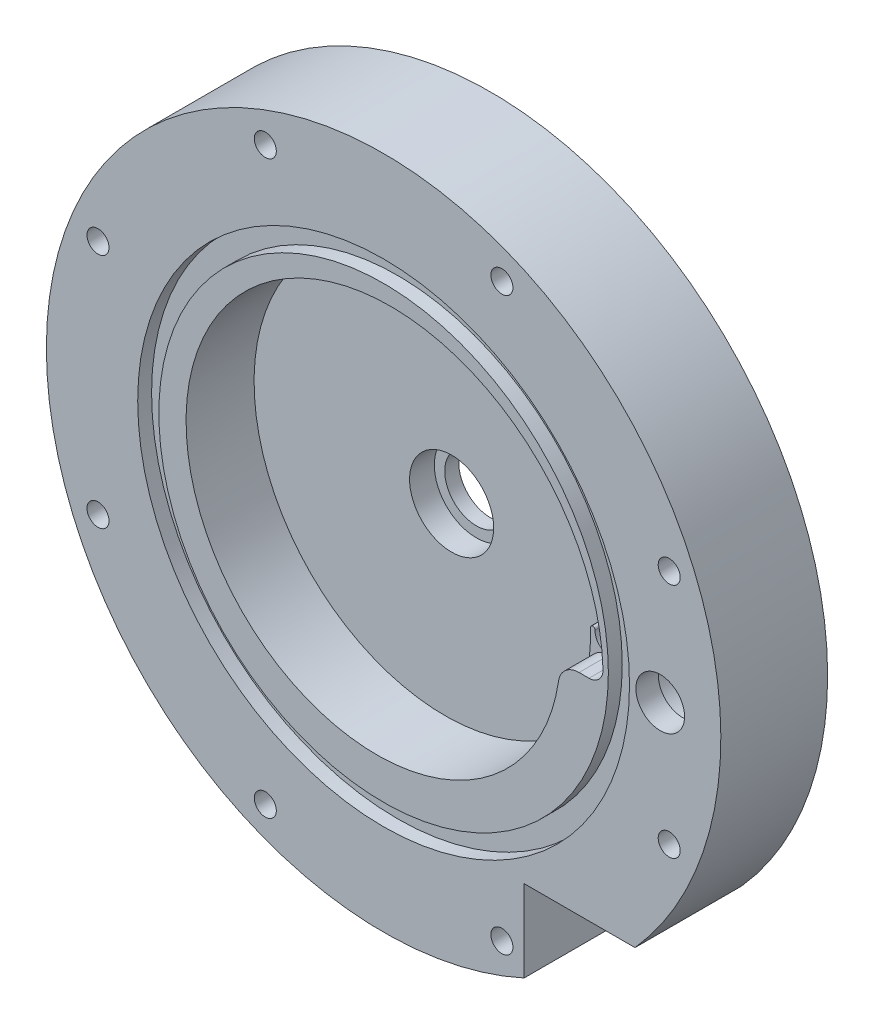
SolidWorks part; units mm, degrees
material "6061-T6 (SS)"
ref_plane "Front Plane" through (0, 0, 0) normal (0, 0, 1) x (1, 0, 0)
ref_plane "Top Plane" through (0, 0, 0) normal (0, 1, 0) x (1, 0, 0)
ref_plane "Right Plane" through (0, 0, 0) normal (1, 0, 0) x (0, 0, -1)
sketch "Sketch22" plane through (0, 0, 0) normal (0, 1, 0) x (1, 0, 0)
  line L0 (-25.4, 0) -> (-9.5, 0)
  line L1 (-25.4, 0) -> (-25.4, -15.367)
  line L3 (-25.4, -15.367) -> (-76.2, -15.367)
  line L4 (-76.2, -15.367) -> (-76.2, 8.763)
  line L5 (-9.5, 0) -> (-9.5, 5.588)
  line L7 (-9.5, 5.588) -> (-7.1437, 5.588)
  line L8 (-7.1437, 5.588) -> (-7.1437, 8.763)
  line L9 (-7.1437, 8.763) -> (-76.2, 8.763)
  line L10 (0, 0) -> (0, 9.525) construction
  dimension "D1" = 14.2875
  dimension "D2" = 19
  dimension "D4" = 3.175
  dimension "D5" = 50.8
  dimension "D6" = 152.4
  dimension "D7" = 24.13
  dimension ".27" = 5.588
revolve "Main Body" add sketch "Sketch22" angle 360 about L10
curve "Volute Spiral"
sketch "Sketch23" plane through (0, 0, 0) normal (0, 0, 1) x (1, 0, 0)
  line L0 (44.1669, -3.2789) -> (46.41, -3.2789)
  arc A1 (40.9936, 0) -> (44.1669, -3.2789) centre (44.1669, -0.1039) ccw
  arc A2 (39.9395, 0) -> (40.9936, 0) centre (40.4666, 0.0173) cw
  arc A4 (46.41, -3.2789) -> (49.578, 0) centre (46.41, -0.1091) ccw
  spline S0 degree 3 poles (2036.7889, 105.1389) (27.9917, 30.1612) (39.5671, 15.0372) (39.954, -0.5026) (39.9588, -0.7541) (39.9652, -1.2573) (39.9616, -2.517) (39.8751, -4.3652) (39.6495, -6.5428) (39.3399, -8.5438) (38.9295, -10.5302) (38.4188, -12.497) (37.8089, -14.4391) (37.1009, -16.3516) (36.2962, -18.2293) (35.3965, -20.0675) (34.4038, -21.8614) (33.3202, -23.6061) (32.1481, -25.2972) (30.8902, -26.9301) (29.5494, -28.5005) (28.1288, -30.0042) (26.6317, -31.4371) (25.0616, -32.7952) (23.4223, -34.075) (21.7176, -35.2728) (19.9517, -36.3854) (18.1288, -37.4095) (16.2533, -38.3423) (14.3299, -39.1811) (12.3632, -39.9234) (10.3581, -40.5669) (8.3195, -41.1098) (6.2525, -41.5501) (4.1622, -41.8865) (2.054, -42.1178) (-0.0671, -42.2429) (-2.1955, -42.2611) (-4.3259, -42.1721) (-6.4529, -41.9757) (-8.5711, -41.6719) (-10.675, -41.2613) (-12.7593, -40.7443) (-14.8186, -40.1221) (-16.8476, -39.3958) (-18.841, -38.5668) (-20.7936, -37.6369) (-22.7003, -36.6081) (-24.5561, -35.4827) (-26.3561, -34.2632) (-28.0956, -32.9524) (-29.7698, -31.5532) (-31.3743, -30.0689) (-32.9048, -28.503) (-34.357, -26.8593) (-35.7272, -25.1415) (-37.0114, -23.3537) (-38.2061, -21.5004) (-39.308, -19.586) (-40.314, -17.615) (-41.221, -15.5925) (-42.0265, -13.5232) (-42.7281, -11.4123) (-43.3237, -9.265) (-43.8112, -7.0867) (-44.1892, -4.8828) (-44.4563, -2.6588) (-44.6113, -0.4202) (-44.6537, 1.8272) (-44.5827, 4.0778) (-44.3982, 6.3259) (-44.1003, 8.5657) (-43.6894, 10.7916) (-43.1661, 12.9978) (-42.5313, 15.1786) (-41.7863, 17.3284) (-40.9326, 19.4417) (-39.9719, 21.5129) (-38.9064, 23.5366) (-37.7384, 25.5075) (-36.4705, 27.4204) (-35.1055, 29.2703) (-33.6468, 31.0522) (-32.0975, 32.7613) (-30.4614, 34.3932) (-28.7423, 35.9432) (-26.9442, 37.4073) (-25.0716, 38.7814) (-23.1289, 40.0617) (-21.1208, 41.2447) (-19.0521, 42.3269) (-16.928, 43.3053) (-14.7537, 44.177) (-12.5345, 44.9396) (-10.2758, 45.5905) (-7.9834, 46.1279) (-5.6629, 46.55) (-3.3202, 46.8552) (-0.9611, 47.0425) (1.4085, 47.1109) (3.7826, 47.06) (6.155, 46.8893) (8.5199, 46.5989) (10.8711, 46.1892) (13.2026, 45.6608) (15.5084, 45.0146) (17.7826, 44.252) (20.0193, 43.3744) (22.2127, 42.3836) (24.357, 41.2819) (26.4467, 40.0717) (28.4762, 38.7556) (30.4402, 37.3367) (32.3334, 35.8182) (34.1508, 34.2036) (35.8876, 32.4968) (37.539, 30.7018) (39.1006, 28.8228) (40.568, 26.8643) (41.9373, 24.8311) (43.2047, 22.7281) (44.3665, 20.5604) (45.4195, 18.3333) (46.3606, 16.0523) (47.1871, 13.7229) (47.8965, 11.351) (48.4866, 8.9424) (48.9555, 6.5032) (49.2727, 4.2452) (49.431, 2.5929) (49.4967, 1.6609) (49.522, 1.2461) (49.539, 0.9348) (49.554, 0.6234) (50.3116, -17.2348) (38.9556, -35.4442) (2048.9371, 22.4075) knots -0.163415 -0.163415 -0.163415 -0.163415 0.000895 0.001791 0.002687 0.003583 0.007168 0.016147 0.023344 0.030554 0.037776 0.045012 0.05226 0.059521 0.066796 0.074083 0.081383 0.088697 0.096023 0.103362 0.110715 0.118081 0.12546 0.132852 0.140257 0.147676 0.155108 0.162553 0.170011 0.177483 0.184968 0.192466 0.199978 0.207503 0.215042 0.222594 0.230159 0.237738 0.245331 0.252937 0.260556 0.268189 0.275836 0.283496 0.291169 0.298857 0.306558 0.314272 0.322 0.329742 0.337497 0.345267 0.353049 0.360846 0.368656 0.37648 0.384318 0.39217 0.400035 0.407914 0.415807 0.423714 0.431634 0.439569 0.447517 0.455479 0.463455 0.471445 0.479449 0.487467 0.495499 0.503544 0.511604 0.519677 0.527765 0.535867 0.543982 0.552112 0.560256 0.568413 0.576585 0.584771 0.592971 0.601185 0.609413 0.617655 0.625911 0.634182 0.642466 0.650765 0.659078 0.667405 0.675747 0.684102 0.692472 0.700856 0.709254 0.717666 0.726093 0.734534 0.742989 0.751459 0.759943 0.768441 0.776953 0.78548 0.794021 0.802577 0.811146 0.819731 0.828329 0.836942 0.845569 0.854211 0.862867 0.871538 0.880223 0.888922 0.897636 0.906365 0.915108 0.923865 0.932637 0.941423 0.950224 0.95904 0.967869 0.976714 0.985573 0.992227 0.994447 0.995557 0.996667 0.997778 0.998889 1.187662 1.187662 1.187662 1.187662 only from (39.9395, 0) to (49.578, 0) construction
  spline S1 degree 3 poles (39.9395, 0) (39.9423, -0.0837) (39.9478, -0.2513) (39.954, -0.5026) (39.9588, -0.7541) (39.9652, -1.2573) (39.9616, -2.517) (39.8751, -4.3652) (39.6495, -6.5428) (39.3399, -8.5438) (38.9295, -10.5302) (38.4188, -12.497) (37.8089, -14.4391) (37.1009, -16.3516) (36.2962, -18.2293) (35.3965, -20.0675) (34.4038, -21.8614) (33.3202, -23.6061) (32.1481, -25.2972) (30.8902, -26.9301) (29.5494, -28.5005) (28.1288, -30.0042) (26.6317, -31.4371) (25.0616, -32.7952) (23.4223, -34.075) (21.7176, -35.2728) (19.9517, -36.3854) (18.1288, -37.4095) (16.2533, -38.3423) (14.3299, -39.1811) (12.3632, -39.9234) (10.3581, -40.5669) (8.3195, -41.1098) (6.2525, -41.5501) (4.1622, -41.8865) (2.054, -42.1178) (-0.0671, -42.2429) (-2.1955, -42.2611) (-4.3259, -42.1721) (-6.4529, -41.9757) (-8.5711, -41.6719) (-10.675, -41.2613) (-12.7593, -40.7443) (-14.8186, -40.1221) (-16.8476, -39.3958) (-18.841, -38.5668) (-20.7936, -37.6369) (-22.7003, -36.6081) (-24.5561, -35.4827) (-26.3561, -34.2632) (-28.0956, -32.9524) (-29.7698, -31.5532) (-31.3743, -30.0689) (-32.9048, -28.503) (-34.357, -26.8593) (-35.7272, -25.1415) (-37.0114, -23.3537) (-38.2061, -21.5004) (-39.308, -19.586) (-40.314, -17.615) (-41.221, -15.5925) (-42.0265, -13.5232) (-42.7281, -11.4123) (-43.3237, -9.265) (-43.8112, -7.0867) (-44.1892, -4.8828) (-44.4563, -2.6588) (-44.6113, -0.4202) (-44.6537, 1.8272) (-44.5827, 4.0778) (-44.3982, 6.3259) (-44.1003, 8.5657) (-43.6894, 10.7916) (-43.1661, 12.9978) (-42.5313, 15.1786) (-41.7863, 17.3284) (-40.9326, 19.4417) (-39.9719, 21.5129) (-38.9064, 23.5366) (-37.7384, 25.5075) (-36.4705, 27.4204) (-35.1055, 29.2703) (-33.6468, 31.0522) (-32.0975, 32.7613) (-30.4614, 34.3932) (-28.7423, 35.9432) (-26.9442, 37.4073) (-25.0716, 38.7814) (-23.1289, 40.0617) (-21.1208, 41.2447) (-19.0521, 42.3269) (-16.928, 43.3053) (-14.7537, 44.177) (-12.5345, 44.9396) (-10.2758, 45.5905) (-7.9834, 46.1279) (-5.6629, 46.55) (-3.3202, 46.8552) (-0.9611, 47.0425) (1.4085, 47.1109) (3.7826, 47.06) (6.155, 46.8893) (8.5199, 46.5989) (10.8711, 46.1892) (13.2026, 45.6608) (15.5084, 45.0146) (17.7826, 44.252) (20.0193, 43.3744) (22.2127, 42.3836) (24.357, 41.2819) (26.4467, 40.0717) (28.4762, 38.7556) (30.4402, 37.3367) (32.3334, 35.8182) (34.1508, 34.2036) (35.8876, 32.4968) (37.539, 30.7018) (39.1006, 28.8228) (40.568, 26.8643) (41.9373, 24.8311) (43.2047, 22.7281) (44.3665, 20.5604) (45.4195, 18.3333) (46.3606, 16.0523) (47.1871, 13.7229) (47.8965, 11.351) (48.4866, 8.9424) (48.9555, 6.5032) (49.2727, 4.2452) (49.431, 2.5929) (49.4967, 1.6609) (49.522, 1.2461) (49.539, 0.9348) (49.554, 0.6234) (49.5673, 0.3117) (49.5744, 0.1039) (49.578, 0) knots 0 0 0 0 0.000895 0.001791 0.002687 0.003583 0.007168 0.016147 0.023344 0.030554 0.037776 0.045012 0.05226 0.059521 0.066796 0.074083 0.081383 0.088697 0.096023 0.103362 0.110715 0.118081 0.12546 0.132852 0.140257 0.147676 0.155108 0.162553 0.170011 0.177483 0.184968 0.192466 0.199978 0.207503 0.215042 0.222594 0.230159 0.237738 0.245331 0.252937 0.260556 0.268189 0.275836 0.283496 0.291169 0.298857 0.306558 0.314272 0.322 0.329742 0.337497 0.345267 0.353049 0.360846 0.368656 0.37648 0.384318 0.39217 0.400035 0.407914 0.415807 0.423714 0.431634 0.439569 0.447517 0.455479 0.463455 0.471445 0.479449 0.487467 0.495499 0.503544 0.511604 0.519677 0.527765 0.535867 0.543982 0.552112 0.560256 0.568413 0.576585 0.584771 0.592971 0.601185 0.609413 0.617655 0.625911 0.634182 0.642466 0.650765 0.659078 0.667405 0.675747 0.684102 0.692472 0.700856 0.709254 0.717666 0.726093 0.734534 0.742989 0.751459 0.759943 0.768441 0.776953 0.78548 0.794021 0.802577 0.811146 0.819731 0.828329 0.836942 0.845569 0.854211 0.862867 0.871538 0.880223 0.888922 0.897636 0.906365 0.915108 0.923865 0.932637 0.941423 0.950224 0.95904 0.967869 0.976714 0.985573 0.992227 0.994447 0.995557 0.996667 0.997778 0.998889 1 1 1 1
  dimension "D1" = 3.175
  dimension "D2" = 1.0541
extrude "Volute Cut" cut sketch "Sketch23" along normal through all
ref_plane "Volute Height Plane" through (0, 0, 8.5827) normal (0, 0, 1) x (1, 0, 0)
sketch "Sketch25" plane through (0, 0, 8.5827) normal (0, 0, 1) x (1, 0, 0)
  arc A0 (44.1669, -3.2789) -> (39.5302, -7.28) centre (44.1669, -7.9661) ccw
  arc A1 (46.41, -3.2789) -> (49.578, 0) centre (46.41, -0.1091) ccw construction
  arc A2 (46.41, -3.2789) -> (49.578, 0) centre (46.41, -0.1091) ccw
  arc A3 (40.9936, 0) -> (39.9395, 0) centre (40.4666, 0.0173) ccw construction
  arc A4 (40.9936, 0) -> (44.1669, -3.2789) centre (44.1669, -0.1039) ccw construction
  arc A5 (40.9936, 0) -> (39.9395, 0) centre (40.4666, 0.0173) ccw
  arc A6 (40.9936, 0) -> (44.1669, -3.2789) centre (44.1669, -0.1039) ccw
  spline S1 degree 3 poles (2048.8734, 22.4056) (38.9558, -35.4438) (50.3115, -17.2346) (49.554, 0.6234) (49.539, 0.9348) (49.522, 1.2461) (49.4967, 1.6609) (49.431, 2.5929) (49.2727, 4.2452) (48.9555, 6.5032) (48.4866, 8.9424) (47.8965, 11.351) (47.1871, 13.7229) (46.3606, 16.0523) (45.4195, 18.3333) (44.3665, 20.5604) (43.2047, 22.7281) (41.9373, 24.8311) (40.568, 26.8643) (39.1006, 28.8228) (37.539, 30.7018) (35.8876, 32.4968) (34.1508, 34.2036) (32.3334, 35.8182) (30.4402, 37.3367) (28.4762, 38.7556) (26.4467, 40.0717) (24.357, 41.2819) (22.2127, 42.3836) (20.0193, 43.3744) (17.7826, 44.252) (15.5084, 45.0146) (13.2026, 45.6608) (10.8711, 46.1892) (8.5199, 46.5989) (6.155, 46.8893) (3.7826, 47.06) (1.4085, 47.1109) (-0.9611, 47.0425) (-3.3202, 46.8552) (-5.6629, 46.55) (-7.9834, 46.1279) (-10.2758, 45.5905) (-12.5345, 44.9396) (-14.7537, 44.177) (-16.928, 43.3053) (-19.0521, 42.3269) (-21.1208, 41.2447) (-23.1289, 40.0617) (-25.0716, 38.7814) (-26.9442, 37.4073) (-28.7423, 35.9432) (-30.4614, 34.3932) (-32.0975, 32.7613) (-33.6468, 31.0522) (-35.1055, 29.2703) (-36.4705, 27.4204) (-37.7384, 25.5075) (-38.9064, 23.5366) (-39.9719, 21.5129) (-40.9326, 19.4417) (-41.7863, 17.3284) (-42.5313, 15.1786) (-43.1661, 12.9978) (-43.6894, 10.7916) (-44.1003, 8.5657) (-44.3982, 6.3259) (-44.5827, 4.0778) (-44.6537, 1.8272) (-44.6113, -0.4202) (-44.4563, -2.6588) (-44.1892, -4.8828) (-43.8112, -7.0867) (-43.3237, -9.265) (-42.7281, -11.4123) (-42.0265, -13.5232) (-41.221, -15.5925) (-40.314, -17.615) (-39.308, -19.586) (-38.2061, -21.5004) (-37.0114, -23.3537) (-35.7272, -25.1415) (-34.357, -26.8593) (-32.9048, -28.503) (-31.3743, -30.0689) (-29.7698, -31.5532) (-28.0956, -32.9524) (-26.3561, -34.2632) (-24.5561, -35.4827) (-22.7003, -36.6081) (-20.7936, -37.6369) (-18.841, -38.5668) (-16.8476, -39.3958) (-14.8186, -40.1221) (-12.7593, -40.7443) (-10.675, -41.2613) (-8.5711, -41.6719) (-6.4529, -41.9757) (-4.3259, -42.1721) (-2.1955, -42.2611) (-0.0671, -42.2429) (2.054, -42.1178) (4.1622, -41.8865) (6.2525, -41.5501) (8.3195, -41.1098) (10.3581, -40.5669) (12.3632, -39.9234) (14.3299, -39.1811) (16.2533, -38.3423) (18.1288, -37.4095) (19.9517, -36.3854) (21.7176, -35.2728) (23.4223, -34.075) (25.0616, -32.7952) (26.6317, -31.4371) (28.1288, -30.0042) (29.5494, -28.5005) (30.8902, -26.9301) (32.1481, -25.2972) (33.3202, -23.6061) (34.4038, -21.8614) (35.3965, -20.0675) (36.2962, -18.2293) (37.1009, -16.3516) (37.8089, -14.4391) (38.4188, -12.497) (38.9295, -10.5302) (39.3399, -8.5438) (39.6495, -6.5428) (39.8751, -4.3652) (39.9616, -2.517) (39.9652, -1.2573) (39.9588, -0.7541) (39.954, -0.5026) (39.5671, 15.0364) (27.9928, 30.1597) (2036.501, 105.1281) knots -0.18766 -0.18766 -0.18766 -0.18766 0.001111 0.002222 0.003333 0.004443 0.005553 0.007773 0.014427 0.023286 0.032131 0.04096 0.049776 0.058577 0.067363 0.076135 0.084892 0.093635 0.102364 0.111078 0.119777 0.128462 0.137133 0.145789 0.154431 0.163058 0.171671 0.180269 0.188854 0.197423 0.205979 0.21452 0.223047 0.231559 0.240057 0.248541 0.257011 0.265466 0.273907 0.282334 0.290746 0.299144 0.307528 0.315898 0.324253 0.332595 0.340922 0.349235 0.357534 0.365818 0.374089 0.382345 0.390587 0.398815 0.407029 0.415229 0.423415 0.431587 0.439744 0.447888 0.456018 0.464133 0.472235 0.480323 0.488396 0.496456 0.504501 0.512533 0.520551 0.528555 0.536545 0.544521 0.552483 0.560431 0.568366 0.576286 0.584193 0.592086 0.599965 0.60783 0.615682 0.62352 0.631344 0.639154 0.646951 0.654733 0.662503 0.670258 0.678 0.685728 0.693442 0.701143 0.708831 0.716504 0.724164 0.731811 0.739444 0.747063 0.754669 0.762262 0.769841 0.777406 0.784958 0.792497 0.800022 0.807534 0.815032 0.822517 0.829989 0.837447 0.844892 0.852324 0.859743 0.867148 0.87454 0.881919 0.889285 0.896638 0.903977 0.911303 0.918617 0.925917 0.933204 0.940479 0.94774 0.954988 0.962224 0.969446 0.976656 0.983853 0.992832 0.996417 0.997313 0.998209 0.999105 1.163407 1.163407 1.163407 1.163407 only from (49.578, 0) to (39.9395, 0) construction
  spline S2 degree 3 poles (49.578, 0) (49.5744, 0.1039) (49.5673, 0.3117) (49.554, 0.6234) (49.539, 0.9348) (49.522, 1.2461) (49.4967, 1.6609) (49.431, 2.5929) (49.2727, 4.2452) (48.9555, 6.5032) (48.4866, 8.9424) (47.8965, 11.351) (47.1871, 13.7229) (46.3606, 16.0523) (45.4195, 18.3333) (44.3665, 20.5604) (43.2047, 22.7281) (41.9373, 24.8311) (40.568, 26.8643) (39.1006, 28.8228) (37.539, 30.7018) (35.8876, 32.4968) (34.1508, 34.2036) (32.3334, 35.8182) (30.4402, 37.3367) (28.4762, 38.7556) (26.4467, 40.0717) (24.357, 41.2819) (22.2127, 42.3836) (20.0193, 43.3744) (17.7826, 44.252) (15.5084, 45.0146) (13.2026, 45.6608) (10.8711, 46.1892) (8.5199, 46.5989) (6.155, 46.8893) (3.7826, 47.06) (1.4085, 47.1109) (-0.9611, 47.0425) (-3.3202, 46.8552) (-5.6629, 46.55) (-7.9834, 46.1279) (-10.2758, 45.5905) (-12.5345, 44.9396) (-14.7537, 44.177) (-16.928, 43.3053) (-19.0521, 42.3269) (-21.1208, 41.2447) (-23.1289, 40.0617) (-25.0716, 38.7814) (-26.9442, 37.4073) (-28.7423, 35.9432) (-30.4614, 34.3932) (-32.0975, 32.7613) (-33.6468, 31.0522) (-35.1055, 29.2703) (-36.4705, 27.4204) (-37.7384, 25.5075) (-38.9064, 23.5366) (-39.9719, 21.5129) (-40.9326, 19.4417) (-41.7863, 17.3284) (-42.5313, 15.1786) (-43.1661, 12.9978) (-43.6894, 10.7916) (-44.1003, 8.5657) (-44.3982, 6.3259) (-44.5827, 4.0778) (-44.6537, 1.8272) (-44.6113, -0.4202) (-44.4563, -2.6588) (-44.1892, -4.8828) (-43.8112, -7.0867) (-43.3237, -9.265) (-42.7281, -11.4123) (-42.0265, -13.5232) (-41.221, -15.5925) (-40.314, -17.615) (-39.308, -19.586) (-38.2061, -21.5004) (-37.0114, -23.3537) (-35.7272, -25.1415) (-34.357, -26.8593) (-32.9048, -28.503) (-31.3743, -30.0689) (-29.7698, -31.5532) (-28.0956, -32.9524) (-26.3561, -34.2632) (-24.5561, -35.4827) (-22.7003, -36.6081) (-20.7936, -37.6369) (-18.841, -38.5668) (-16.8476, -39.3958) (-14.8186, -40.1221) (-12.7593, -40.7443) (-10.675, -41.2613) (-8.5711, -41.6719) (-6.4529, -41.9757) (-4.3259, -42.1721) (-2.1955, -42.2611) (-0.0671, -42.2429) (2.054, -42.1178) (4.1622, -41.8865) (6.2525, -41.5501) (8.3195, -41.1098) (10.3581, -40.5669) (12.3632, -39.9234) (14.3299, -39.1811) (16.2533, -38.3423) (18.1288, -37.4095) (19.9517, -36.3854) (21.7176, -35.2728) (23.4223, -34.075) (25.0616, -32.7952) (26.6317, -31.4371) (28.1288, -30.0042) (29.5494, -28.5005) (30.8902, -26.9301) (32.1481, -25.2972) (33.3202, -23.6061) (34.4038, -21.8614) (35.3965, -20.0675) (36.2962, -18.2293) (37.1009, -16.3516) (37.8089, -14.4391) (38.4188, -12.497) (38.9295, -10.5302) (39.3399, -8.5438) (39.6495, -6.5428) (39.8751, -4.3652) (39.9616, -2.517) (39.9652, -1.2573) (39.9588, -0.7541) (39.954, -0.5026) (39.9478, -0.2513) (39.9423, -0.0837) (39.9395, 0) knots 0 0 0 0 0.001111 0.002222 0.003333 0.004443 0.005553 0.007773 0.014427 0.023286 0.032131 0.04096 0.049776 0.058577 0.067363 0.076135 0.084892 0.093635 0.102364 0.111078 0.119777 0.128462 0.137133 0.145789 0.154431 0.163058 0.171671 0.180269 0.188854 0.197423 0.205979 0.21452 0.223047 0.231559 0.240057 0.248541 0.257011 0.265466 0.273907 0.282334 0.290746 0.299144 0.307528 0.315898 0.324253 0.332595 0.340922 0.349235 0.357534 0.365818 0.374089 0.382345 0.390587 0.398815 0.407029 0.415229 0.423415 0.431587 0.439744 0.447888 0.456018 0.464133 0.472235 0.480323 0.488396 0.496456 0.504501 0.512533 0.520551 0.528555 0.536545 0.544521 0.552483 0.560431 0.568366 0.576286 0.584193 0.592086 0.599965 0.60783 0.615682 0.62352 0.631344 0.639154 0.646951 0.654733 0.662503 0.670258 0.678 0.685728 0.693442 0.701143 0.708831 0.716504 0.724164 0.731811 0.739444 0.747063 0.754669 0.762262 0.769841 0.777406 0.784958 0.792497 0.800022 0.807534 0.815032 0.822517 0.829989 0.837447 0.844892 0.852324 0.859743 0.867148 0.87454 0.881919 0.889285 0.896638 0.903977 0.911303 0.918617 0.925917 0.933204 0.940479 0.94774 0.954988 0.962224 0.969446 0.976656 0.983853 0.992832 0.996417 0.997313 0.998209 0.999105 1 1 1 1
extrude "Cap Cut" cut sketch "Sketch25" along normal through all contours A2 S2 A5 A6 | S2 A6 A5 region at (40.8724, -2.704, 8.5827)
sketch "Sketch28" plane through (0, 0, 15.367) normal (0, 0, 1) x (1, 0, 0)
  line L1 (31.75, -69.2703) -> (56.7961, -69.2703)
  line L2 (31.75, -69.2703) -> (31.75, -50.8)
  line L3 (31.75, -50.8) -> (56.7961, -50.8)
  line L4 (56.7961, -69.2703) -> (56.7961, -50.8)
  circle A0 centre (0, 0) radius 76.2 construction
  dimension "D1" = 50.8
  dimension "D2" = 31.75
extrude "Outlet Hole Cut" cut sketch "Sketch28" against normal through all
hole_wizard "Outlet Hole" positions "3DSketch2" profile "Sketch20" hole size "3/8" standard "ANSI Inch"
sketch3d "3DSketch2"
  line L0 (46.41, -3.2789, 0) -> (44.1669, -3.2789, 8.5827) construction
  point P0 (45.2885, -3.2789, 4.2913)
  point P11 (45.2885, -3.2789, 4.2913)
  point P20 (45.2885, -3.2789, 4.2913)
  point P22 (45.2885, -50.8, 4.2913)
sketch "Sketch20" plane through (45.2885, -50.8, 4.2913) normal (1, 0, 0) x (0, 0, -1)
  line L0 (0, 0) -> (0, 53.6616)
  line L1 (0, 53.6616) -> (4.7625, 50.8)
  line L2 (4.7625, 50.8) -> (4.7625, 0)
  line L5 (4.7625, 0) -> (0, 0)
  line L10 (0, 53.6616) -> (-4.7625, 50.8) construction
  line L11 (0, -6.35) -> (0, 107.95) construction
  dimension "Hole Dia." = 9.525
  dimension "Hole Depth" = 50.8
  dimension "Drill Angle" = 118
hole_wizard "Outlet Pipe Thread" positions "3DSketch3" profile "Sketch21" hole size "3/8" standard "ANSI Inch"
sketch3d "3DSketch3"
  line L0 (40.526, -50.8, 4.2913) -> (50.051, -50.8, 4.2913) construction
  line L2 (45.2885, -50.8, -0.4712) -> (45.2885, -50.8, 9.0538) construction
  circle A4 centre (45.2885, -50.8, 4.2913) radius 4.7625 construction
  point P2 (45.2885, -50.8, 4.2913)
  point P38 (45.2885, -55.5625, 4.2913)
sketch "Sketch21" plane through (45.2885, -50.8, 4.2913) normal (1, 0, 0) x (0, 0, -1)
  line L0 (0, 0) -> (0, 16.9886)
  line L1 (0, 16.9886) -> (7.1374, 12.7)
  line L2 (7.1374, 12.7) -> (7.1374, 0)
  line L5 (7.1374, 0) -> (0, 0)
  line L10 (0, 16.9886) -> (-7.1374, 12.7) construction
  line L11 (0, -6.35) -> (0, 107.95) construction
  dimension "Hole Dia." = 14.2748
  dimension "Hole Depth" = 12.7
  dimension "Drill Angle" = 118
sketch "Sketch26" plane through (0, 0, 15.367) normal (0, 0, 1) x (1, 0, 0)
  line L0 (64.533, -26.7304) -> (70.3996, -29.1605) construction
  line L1 (76.2, 0) -> (0, 0) construction
  circle A0 centre (64.533, -26.7304) radius 2.4892
  circle A1 centre (0, 0) radius 76.2 construction
  dimension "D1" = 4.9784
  dimension "D2" = 6.35
  dimension "D3" = 22.5
extrude "Fastener Hole" cut sketch "Sketch26" against normal through all
pattern_circular "Fastener Holes" count 8 over 360 about axis through (0, 0, 0) along (0, 0, 1) of "Fastener Hole"
ref_axis "Axis1" through (0, 0, -8.763) along (0, 0, 1)
ref_plane "Plane1" through (0, 0, 0) normal (0, 1, 0) x (0, 0, 1)
sketch "Sketch16" plane through (0, 0, 15.367) normal (0, 0, 1) x (1, 0, 0)
  circle A0 centre (0, 0) radius 50.7873
  circle A1 centre (0, 0) radius 55.5625
  dimension "D1" = 4.7752
  dimension "D2" = 111.125
extrude "O-Ring Groove" cut sketch "Sketch16" against normal blind 3.1369
sketch "Sketch27" plane through (0, 0, 0) normal (0, 1, 0) x (0, 0, 1)
  line L1 (3.937, 70.4375) -> (10.287, 70.4375)
  line L2 (-8.763, 76.2) -> (-8.763, -76.2) construction
  line L3 (-8.763, 73.676) -> (3.937, 73.676)
  line L4 (3.937, 73.676) -> (3.937, 70.4375)
  line L8 (10.287, 54.5625) -> (3.937, 54.5625)
  line L9 (3.937, 54.5625) -> (3.937, 51.324)
  line L10 (3.937, 51.324) -> (-8.763, 51.324)
  line L12 (15.367, 62.5) -> (-8.763, 62.5)
  line L13 (-8.763, 73.676) -> (-8.763, 51.324)
  line L14 (10.287, 70.4375) -> (10.287, 68)
  line L15 (10.287, 68) -> (15.367, 68)
  line L16 (15.367, 68) -> (15.367, 57)
  line L17 (15.367, 57) -> (10.287, 57)
  line L18 (10.287, 57) -> (10.287, 54.5625)
  line L19 (15.367, -55.5625) -> (15.367, 55.5625) construction
  dimension "D1" = 6.35
  dimension "D2" = 22.352
  dimension "D3" = 62.5
  dimension "D4" = 12.7
  dimension "D5" = 15.875
  dimension "D6" = 11
revolve "Turbine Shaft Hole" cut sketch "Sketch27" angle 360 about L12 region at (57.6425, 0, 1.6995)
